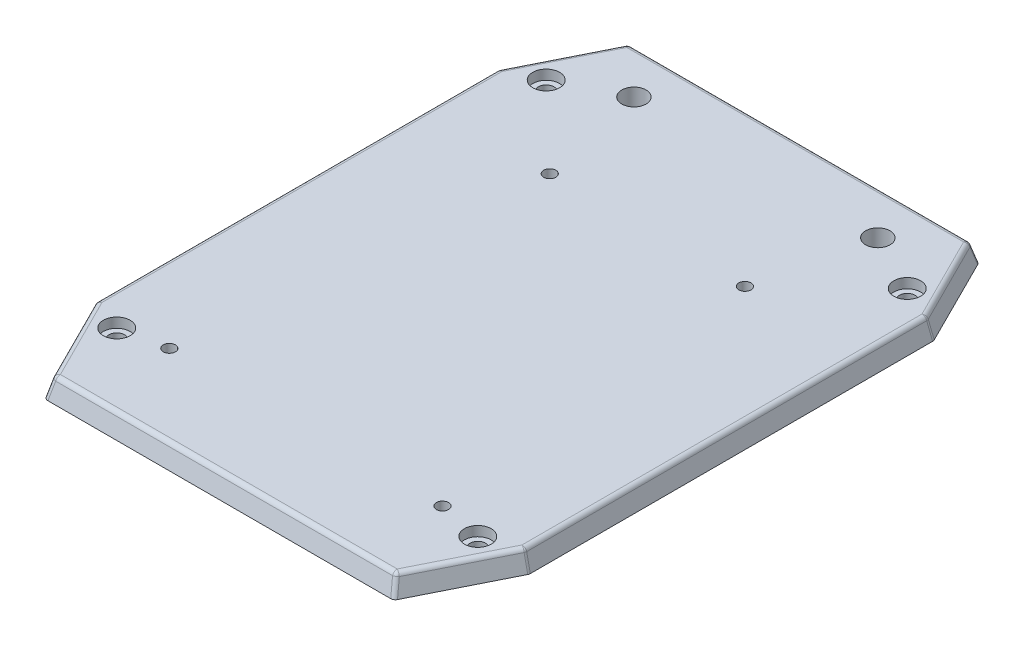
SolidWorks part; units mm, degrees
material "ABS"
ref_plane "Front" through (0, 0, 0) normal (0, 0, 1) x (1, 0, 0)
ref_plane "Top" through (0, 0, 0) normal (0, 1, 0) x (1, 0, 0)
ref_plane "Right" through (0, 0, 0) normal (1, 0, 0) x (0, 0, -1)
sketch "Sketch1" plane through (0, 0, 0) normal (0, 1, 0) x (1, 0, 0)
  line L0 (-45, -41.459) -> (-35.7295, -60)
  line L1 (-45, 60) -> (45, 60) construction
  line L2 (-45, 60) -> (-45, -60) construction
  line L3 (-45, -60) -> (45, -60) construction
  line L4 (45, 60) -> (45, -60) construction
  line L5 (-45, 60) -> (45, -60) construction
  line L6 (-45, -60) -> (45, 60) construction
  line L7 (0, 60) -> (0, -60) construction
  line L8 (-45, 0) -> (45, 0) construction
  line L9 (45, -41.459) -> (35.7295, -60)
  line L10 (45, 41.459) -> (35.7295, 60)
  line L11 (-45, 41.459) -> (-35.7295, 60)
  line L12 (-45, 41.459) -> (-45, -41.459)
  line L13 (-35.7295, -60) -> (35.7295, -60)
  line L14 (45, -41.459) -> (45, 41.459)
  line L15 (-35.7295, 60) -> (35.7295, 60)
  point P0 (0, 0)
  dimension "D1" = 90
  dimension "D2" = 120
  dimension "D3" = 9.2705
  dimension "D4" = 18.541
extrude "Boss-Extrude1" add sketch "Sketch1" along normal mid plane 4
chamfer "Chamfer1" distance 4 angle 16.7 8 edges at (-40.3647, 2, -50.7295) (0, 2, -60) (40.3647, 2, -50.7295) (45, 2, 0) (40.3647, 2, 50.7295) (0, 2, 60) (-40.3647, 2, 50.7295) (-45, 2, 0) first distance on face at (-40.3647, 0, -50.7295) first distance on face at (0, 0, -60) first distance on face at (40.3647, 0, -50.7295) first distance on face at (45, 0, 0) first distance on face at (40.3647, 0, 50.7295) first distance on face at (0, 0, 60) first distance on face at (-40.3647, 0, 50.7295) first distance on face at (-45, 0, 0)
sketch "Sketch2" plane through (0, -2, 0) normal (0, -1, 0) x (1, 0, 0)
  circle A0 centre (-37.0106, 44.0213) radius 1.4 construction
  circle A1 centre (-37.0106, 44.0213) radius 1.4 construction
  circle A2 centre (-37.0106, 44.0213) radius 1.6
  dimension "D1" = 3.2
extrude "Cut-Extrude1" cut sketch "Sketch2" against normal through all
sketch "Sketch3" plane through (0, 2, 0) normal (0, 1, 0) x (1, 0, 0)
  circle A0 centre (-37.0106, -44.0213) radius 2.75
  dimension "D1" = 5.5
extrude "Cut-Extrude2" cut sketch "Sketch3" against normal blind 2
mirror "Mirror1" about plane through (0, 0, 0) normal (1, 0, 0) of "Cut-Extrude2", "Cut-Extrude1"
mirror "Mirror2" about plane through (0, 0, 0) normal (0, 0, 1) of "Mirror1"
fillet "Fillet1" radius 1 16 edges at (35.3587, 0, -59.4) (39.3939, 2, -49.9878) (44.4, 0, -41.3173) (-39.3939, 2, -49.9878) (0, 2, -58.7999) (-44.4, 0, -41.3173) (-35.3587, 0, -59.4) (-44.4, 0, 41.3173) (-35.3587, 0, 59.4) (-43.7999, 2, 0) (-39.3939, 2, 49.9878) (0, 2, 58.7999) (43.7999, 2, 0) (39.3939, 2, 49.9878) (44.4, 0, 41.3173) (35.3587, 0, 59.4)
sketch "Sketch4" plane through (0, 2, 0) normal (0, 1, 0) x (1, 0, 0)
  circle A0 centre (-20, 27.75) radius 1.25 construction
  circle A1 centre (-28, -42.25) radius 1.25 construction
  circle A2 centre (20, 27.75) radius 1.25 construction
  circle A3 centre (28, -42.25) radius 1.25 construction
  circle A4 centre (-20, 27.75) radius 1.25
  circle A5 centre (-28, -42.25) radius 1.25
  circle A6 centre (20, 27.75) radius 1.25
  circle A7 centre (28, -42.25) radius 1.25
extrude "Cut-Extrude3" cut sketch "Sketch4" against normal through all
sketch "Sketch5" plane through (0, -2, 0) normal (0, -1, 0) x (1, 0, 0)
  line L0 (45, -50) -> (-45, -50) construction
  line L1 (45, 41.2329) -> (45, -41.2329) construction
  line L2 (-45, -41.2329) -> (-45, 41.2329) construction
  line L3 (0, 60) -> (0, -60) construction
  line L4 (-35.1375, 60) -> (35.1375, 60) construction
  line L5 (35.1375, -60) -> (-35.1375, -60) construction
  circle A0 centre (25, -50) radius 2.5
  circle A1 centre (-25, -50) radius 2.5
  dimension "D2" = 5
  dimension "D1" = 10
  dimension "D3" = 50
extrude "Cut-Extrude4" cut sketch "Sketch5" against normal through all
